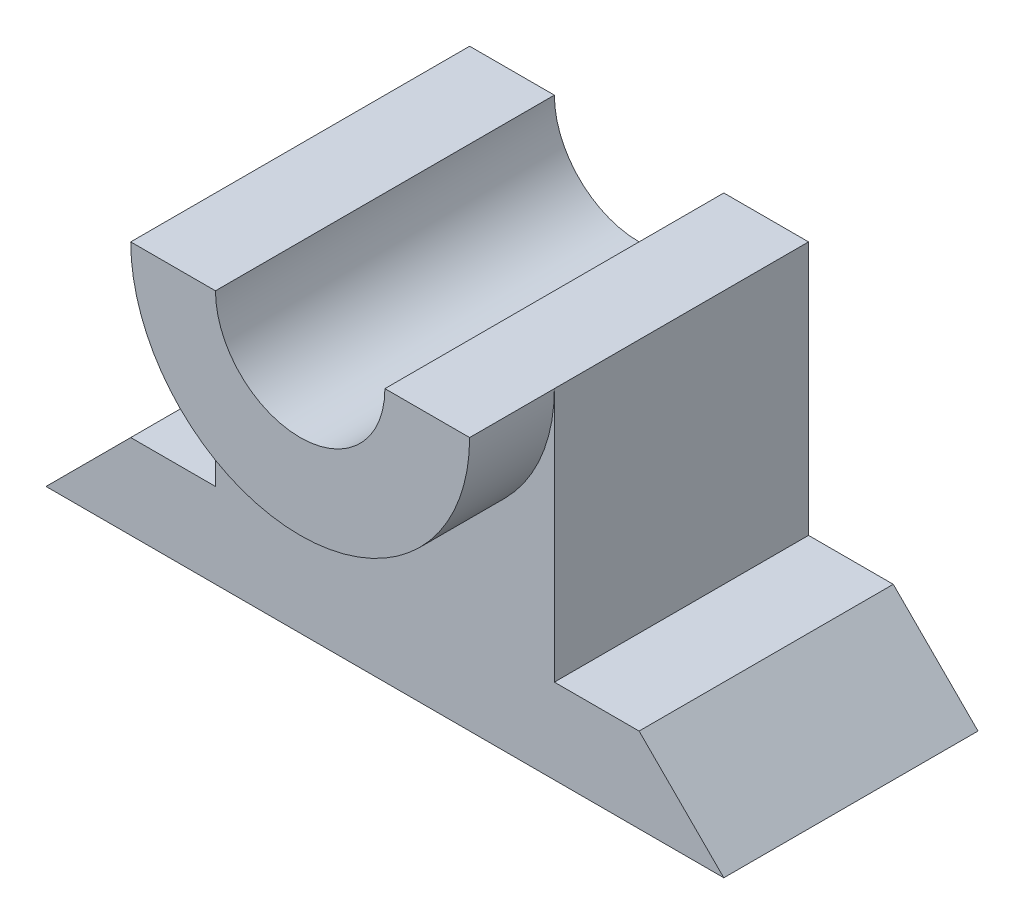
SolidWorks part; units mm, degrees
ref_plane "Front Plane" through (0, 0, 0) normal (0, 0, 1) x (1, 0, 0)
ref_plane "Top Plane" through (0, 0, 0) normal (0, 1, 0) x (1, 0, 0)
ref_plane "Right Plane" through (0, 0, 0) normal (1, 0, 0) x (0, 0, -1)
sketch "Sketch1" plane through (0, 0, 0) normal (0, 0, 1) x (1, 0, 0)
  line L0 (-20, 0) -> (-20, -30)
  line L1 (-20, -30) -> (-30, -30)
  line L2 (-30, -30) -> (-40, -40)
  line L3 (-40, -40) -> (40, -40)
  line L4 (-20, 0) -> (20, 0) construction
  line L5 (0, 0) -> (0, -40) construction
  line L6 (30, -30) -> (40, -40)
  line L7 (20, -30) -> (30, -30)
  line L8 (20, 0) -> (20, -30)
  line L9 (-20, 0) -> (-10, 0)
  line L10 (10, 0) -> (20, 0)
  arc A0 (-10, 0) -> (10, 0) centre (0, 0) ccw
  arc A1 (-20, 0) -> (20, 0) centre (0, 0) ccw
  dimension "D1" = 20
  dimension "D2" = 45
  dimension "D3" = 10
  dimension "D4" = 40
  dimension "D5" = 80
  dimension "D6" = 40
extrude "Boss-Extrude7" add sketch "Sketch1" against normal blind 30 contours L9 A1 L10 A0 | A1 L0 L1 L2 L3 L6 L7 L8 region at (0, -29.3575, 0) region at (-15, -0.4472, 0)
extrude "Boss-Extrude8" add sketch "Sketch1<11>" along normal blind 10 contours L9 A1 L10 A0 region at (-15, -0.4472, 0)
sketch "Sketch1<11>" plane through (0, 0, 0) normal (0, 0, 1) x (1, 0, 0) same geometry as "Sketch1"
